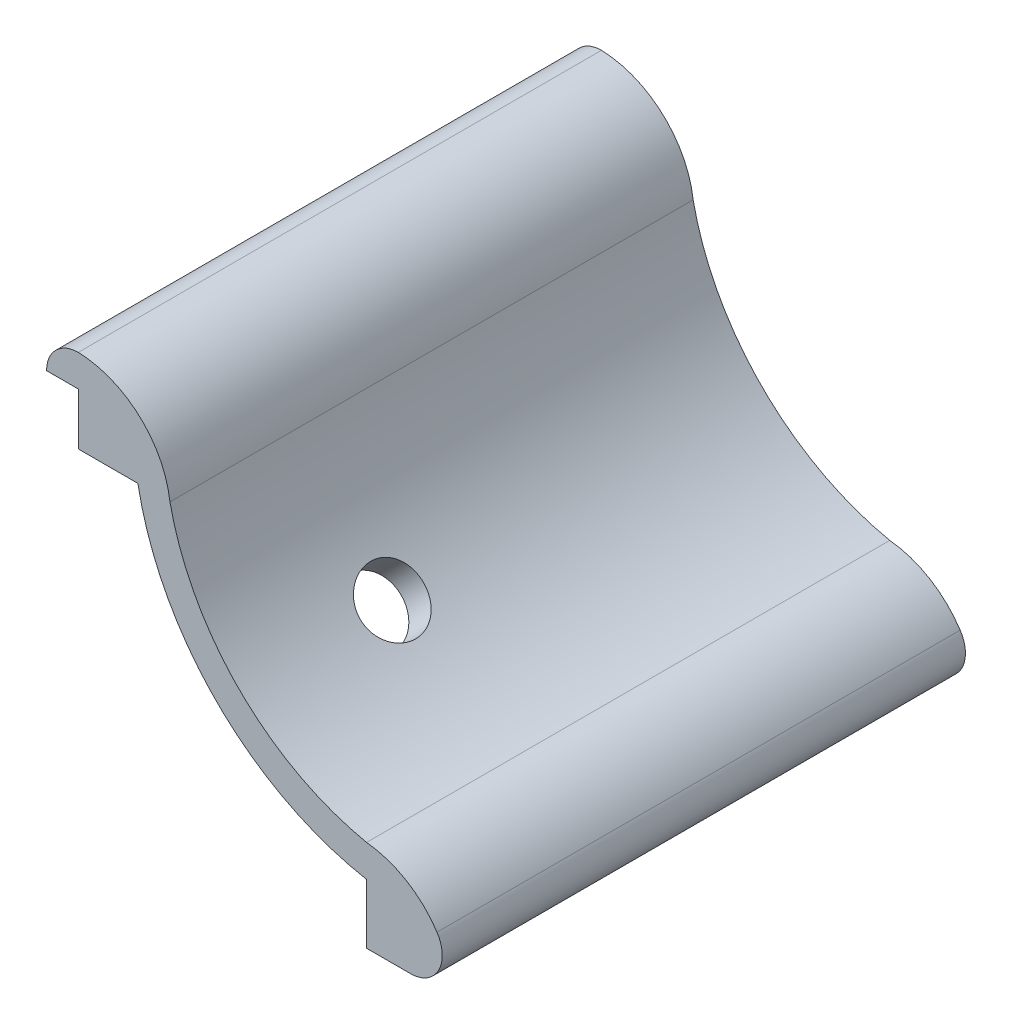
SolidWorks part; units mm, degrees
ref_plane "Front Plane" through (0, 0, 0) normal (0, 0, 1) x (1, 0, 0)
ref_plane "Top Plane" through (0, 0, 0) normal (0, 1, 0) x (1, 0, 0)
ref_plane "Right Plane" through (0, 0, 0) normal (1, 0, 0) x (0, 0, -1)
sketch "Sketch1" plane through (0, 0, 0) normal (0, 0, 1) x (1, 0, 0)
  line L4 (-45.7962, 45.7962) -> (0, 45.7962) construction
  line L6 (0, 45.7962) -> (0, 0) construction
  line L7 (-58.2422, 56.2102) -> (-58.2422, 62.5602)
  line L8 (10.922, -12.446) -> (17.272, -12.446)
  line L9 (-58.2422, 56.2102) -> (-58.2422, 45.7962) construction
  line L10 (-58.2422, 45.7962) -> (-45.7962, 45.7962) construction
  line L11 (0, 0) -> (0, -12.446) construction
  line L12 (0, -12.446) -> (10.922, -12.446) construction
  arc A6 (0, 0) -> (-45.7962, 45.7962) centre (10.3996, 56.1958) cw
  arc A7 (-45.7962, 45.7962) -> (-58.2422, 56.2102) centre (-58.3145, 43.4796) ccw
  arc A8 (0, 0) -> (10.922, -12.446) centre (-1.8079, -12.6018) cw
  arc A9 (-58.2422, 62.5602) -> (-39.3749, 45.7962) centre (-58.3145, 43.4796) cw
  arc A10 (-39.3749, 45.7962) -> (0, 6.4213) centre (10.3996, 56.1958) ccw
  arc A11 (0, 6.4213) -> (17.272, -12.446) centre (-1.8793, -12.6385) cw
  dimension "D1" = 45.7962
  dimension "D2" = 57.15
  dimension "D3" = 10.414
  dimension "D5" = 12.446
  dimension "D4" = 6.35
  dimension "D6" = 12.446
  dimension "D7" = 10.922
extrude "Boss-Extrude1" add sketch "Sketch1" along normal mid plane 209.55 contours L4 | A11 L8 A8 A6 A7 L7 A9 A10
sketch "Sketch2" plane through (0, 0, 0) normal (0, 0, 1) x (1, 0, 0)
  line L0 (-58.2422, 56.2102) -> (-58.2422, 45.7962)
  line L1 (-58.2422, 45.7962) -> (-45.7962, 45.7962)
  line L2 (0, 0) -> (0, -12.446)
  line L3 (0, -12.446) -> (10.922, -12.446)
  arc A0 (-45.7962, 45.7962) -> (-58.2422, 56.2102) centre (-58.3145, 43.4796) ccw construction
  arc A1 (-45.7962, 45.7962) -> (0, 0) centre (10.3996, 56.1958) ccw construction
  arc A2 (-58.2422, 56.2102) -> (-45.7962, 45.7962) centre (-58.3145, 43.4796) cw
  arc A3 (0, 0) -> (10.922, -12.446) centre (-1.8079, -12.6018) cw
extrude "Boss-Extrude2" add sketch "Sketch2" along normal mid plane 185.1914
sketch "Sketch3" plane through (0, 0, -104.775) normal (0, 0, -1) x (-1, 0, 0)
  line L0 (58.2422, 56.2102) -> (58.2422, 45.7962)
  line L1 (58.2422, 45.7962) -> (45.7962, 45.7962)
  line L2 (0, 0) -> (0, -12.446)
  line L3 (0, -12.446) -> (-10.922, -12.446)
  arc A0 (-10.922, -12.446) -> (0, 0) centre (1.8079, -12.6018) cw
  arc A1 (45.7962, 45.7962) -> (58.2422, 56.2102) centre (58.3145, 43.4796) cw
extrude "Boss-Extrude3" add sketch "Sketch3" against normal offset from surface (5.8293 mm away) 6.35 up to face at (-53.4687, 50.0142, -92.5957)
sketch "Sketch4" plane through (0, 0, 104.775) normal (0, 0, 1) x (1, 0, 0)
  line L0 (-58.2422, 56.2102) -> (-58.2422, 45.7962)
  line L1 (-58.2422, 45.7962) -> (-45.7962, 45.7962)
  line L2 (0, 0) -> (0, -12.446)
  line L3 (0, -12.446) -> (10.922, -12.446)
  arc A0 (-58.2422, 56.2102) -> (-45.7962, 45.7962) centre (-58.3145, 43.4796) cw
  arc A1 (0, 0) -> (10.922, -12.446) centre (-1.8079, -12.6018) cw
extrude "Boss-Extrude4" add sketch "Sketch4" against normal blind 6.35
sketch "Sketch5" plane through (0, 0, 104.775) normal (0, 0, 1) x (1, 0, 0)
  line L0 (-58.2422, 45.7962) -> (-58.2422, 62.5602) construction
  line L2 (-57.7342, 44.7636) -> (-65.5217, 44.7636)
  line L3 (-57.7342, 44.7636) -> (-57.7342, 64.5974)
  line L4 (-57.7342, 64.5974) -> (-65.5217, 64.5974)
  line L5 (-65.5217, 44.7636) -> (-65.5217, 64.5974)
  line L6 (-3.152, -11.938) -> (19.6021, -11.938)
  line L7 (-3.152, -11.938) -> (-3.152, -15.345)
  line L8 (-3.152, -15.345) -> (19.6021, -15.345)
  line L9 (19.6021, -11.938) -> (19.6021, -15.345)
  line L10 (0, -12.446) -> (17.272, -12.446) construction
  dimension "D1" = 0.508
  dimension "D2" = 0.508
extrude "Cut-Extrude1" cut sketch "Sketch5" against normal through all
ref_plane "Plane1" through (-5.969, -5.969, 0) normal (-0.7071, -0.7071, 0) x (-0.7071, 0.7071, 0)
sketch "Sketch6" plane through (-5.969, -5.969, 0) normal (-0.7071, -0.7071, 0) x (-0.7071, 0.7071, 0)
  line L0 (0, -74.1654) -> (64.7656, -74.1654) construction
  line L1 (0, -92.5957) -> (0, 92.5957) construction
  line L2 (64.7656, -92.5957) -> (64.7656, 92.5957) construction
  circle A0 centre (32.3828, -74.1654) radius 6.35
  point P9 (32.3828, -74.1654)
  dimension "D1" = 12.7
extrude "Cut-Extrude2" cut sketch "Sketch6" against normal mid plane 12.7
sketch "Sketch7" plane through (0, 0, -104.775) normal (0, 0, -1) x (-1, 0, 0)
  line L5 (-29.4732, 71.2395) -> (81.5811, 71.2395)
  line L6 (-29.4732, 71.2395) -> (-29.4732, -18.4066)
  line L7 (-29.4732, -18.4066) -> (81.5811, -18.4066)
  line L8 (81.5811, 71.2395) -> (81.5811, -18.4066)
extrude "Cut-Extrude3" cut sketch "Sketch7" against normal blind 104.775
sketch "Sketch8" plane through (-57.7342, 0, 0) normal (-1, 0, 0) x (0, 0, 1)
  line L0 (104.775, 45.7962) -> (104.775, 62.5515) construction
  line L1 (0, 62.5515) -> (104.775, 62.5515)
  line L2 (0, 62.5515) -> (0, 56.1972)
  line L3 (0, 56.1972) -> (104.775, 56.1972)
  line L4 (104.775, 62.5515) -> (104.775, 56.1972)
  line L5 (92.5957, 56.1972) -> (98.425, 56.1972) construction
  point P9 (95.5103, 56.1972)
extrude "Boss-Extrude5" add sketch "Sketch8" along normal blind 6.35
fillet "Fillet1" radius 6.35 2 edges at (-64.0842, 62.5515, 52.3875) (17.2602, -11.938, 52.3875)
